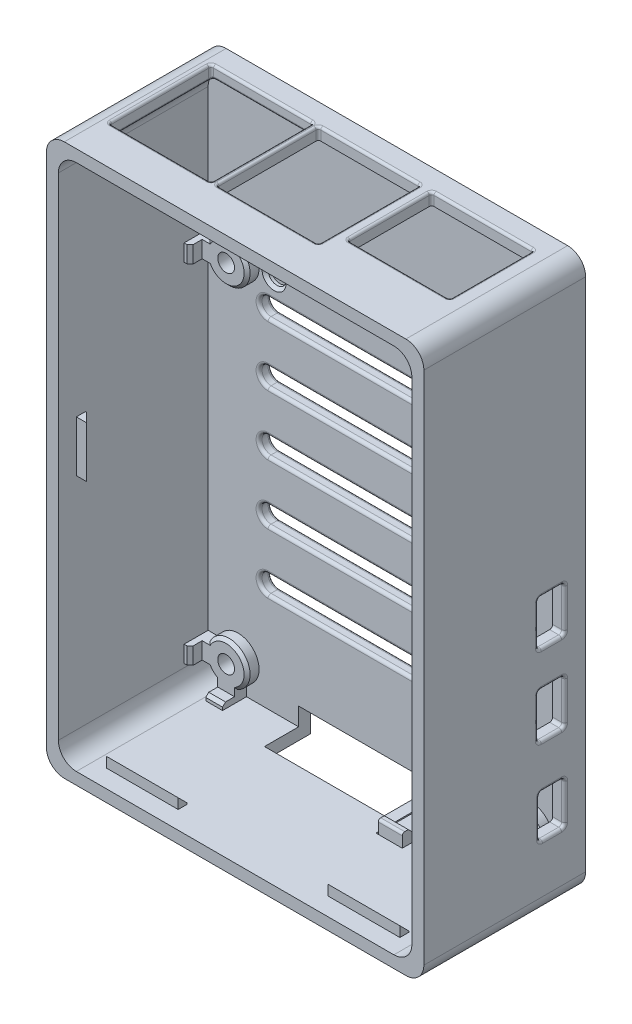
SolidWorks part; units mm, degrees
ref_plane "Front Plane" through (0, 0, 0) normal (1, 0, 0) x (0, 1, 0)
ref_plane "Top Plane" through (0, 0, 0) normal (0, 0, 1) x (0, 1, 0)
ref_plane "Right Plane" through (0, 0, 0) normal (0, 1, 0) x (-1, 0, 0)
sketch "Sketch2" plane through (0, 0, 0) normal (0, 0, 1) x (0, 1, 0)
  line L0 (14.7849, 61.5661) -> (117.7419, 61.5661) construction
  line L1 (-0.0095, 29.4958) -> (120.0951, 29.4958) construction
  line L2 (2.9905, 58.9958) -> (84.9905, 58.9958)
  line L3 (-0.0095, 55.9958) -> (-0.0095, 2.9958)
  line L4 (2.9905, -0.0042) -> (84.9905, -0.0042)
  line L5 (87.9905, 55.9958) -> (87.9905, 2.9958)
  line L6 (33.9905, 95.81) -> (33.9905, -24.3082) construction
  line L7 (43.9905, 95.8142) -> (43.9905, -24.3041) construction
  line L8 (62.9905, 69.2818) -> (62.9905, -9.286) construction
  line L9 (67.9905, 48.9958) -> (67.9905, 9.9958) construction
  line L10 (69.4905, 48.9958) -> (69.4905, 9.9958)
  line L11 (66.4905, 48.9958) -> (66.4905, 9.9958)
  line L12 (57.9905, 48.9958) -> (57.9905, 9.9958) construction
  line L13 (56.4905, 48.9958) -> (56.4905, 9.9958)
  line L14 (59.4905, 48.9958) -> (59.4905, 9.9958)
  line L18 (52.9905, 69.2818) -> (52.9905, -9.286) construction
  line L19 (47.9905, 48.9958) -> (47.9905, 9.9958) construction
  line L20 (49.4905, 48.9958) -> (49.4905, 9.9958)
  line L21 (46.4905, 48.9958) -> (46.4905, 9.9958)
  line L22 (42.9905, 69.2818) -> (42.9905, -9.286) construction
  line L23 (37.9905, 48.9958) -> (37.9905, 9.9958) construction
  line L24 (36.4905, 48.9958) -> (36.4905, 9.9958)
  line L25 (39.4905, 48.9958) -> (39.4905, 9.9958)
  line L26 (32.9905, 69.2818) -> (32.9905, -9.286) construction
  line L27 (27.9905, 48.9958) -> (27.9905, 9.9958) construction
  line L28 (29.4905, 48.9958) -> (29.4905, 9.9958)
  line L29 (26.4905, 48.9958) -> (26.4905, 9.9958)
  line L30 (22.9905, 69.2818) -> (22.9905, -9.286) construction
  line L31 (17.9905, 48.9958) -> (17.9905, 9.9958) construction
  line L32 (16.4905, 48.9958) -> (16.4905, 9.9958)
  line L33 (19.4905, 48.9958) -> (19.4905, 9.9958)
  line L34 (3.5905, 58.9958) -> (3.5905, 57.2036)
  line L35 (0.9905, 60.9958) -> (86.9905, 60.9958)
  line L36 (-2.0095, 57.9958) -> (-2.0095, 0.9958)
  line L37 (0.9905, -2.0042) -> (86.9905, -2.0042)
  line L38 (89.9905, 57.9958) -> (89.9905, 0.9958)
  line L39 (6.3905, 58.9958) -> (6.3905, 57.2036)
  line L40 (3.5905, 57.9958) -> (6.3905, 57.9958)
  line L41 (3.5905, 0.9958) -> (6.3905, 0.9958)
  line L42 (6.3905, -0.0042) -> (6.3905, 1.788)
  line L43 (3.5905, -0.0042) -> (3.5905, 1.788)
  line L44 (64.3905, 0.9958) -> (61.5905, 0.9958)
  line L45 (64.3905, -0.0042) -> (64.3905, 1.788)
  line L46 (61.5905, -0.0042) -> (61.5905, 1.788)
  line L47 (64.3905, 58.9958) -> (64.3905, 57.2036)
  line L48 (64.3905, 57.9958) -> (61.5905, 57.9958)
  line L49 (61.5905, 58.9958) -> (61.5905, 57.2036)
  line L50 (-0.0095, 55.3958) -> (1.7827, 55.3958)
  line L51 (10.4268, 53.9958) -> (-6.5581, 53.9958) construction
  line L52 (-0.0095, 52.5958) -> (1.7827, 52.5958)
  line L53 (0.9905, 55.3958) -> (0.9905, 52.5958)
  line L54 (0.9905, 3.5958) -> (0.9905, 6.3958)
  line L55 (-0.0095, 3.5958) -> (1.7827, 3.5958)
  line L56 (-0.0095, 6.3958) -> (1.7827, 6.3958)
  circle A0 centre (4.9905, 53.9958) radius 1.4
  circle A1 centre (4.9905, 4.9958) radius 1.4
  circle A2 centre (62.9905, 4.9958) radius 1.4
  circle A3 centre (62.9905, 53.9958) radius 1.4
  arc A4 (3.5905, 57.2036) -> (1.7827, 55.3958) centre (4.9905, 53.9958) ccw
  arc A7 (3.5905, 1.788) -> (1.7827, 3.5958) centre (4.9905, 4.9958) cw
  arc A8 (64.3905, 1.788) -> (61.5905, 1.788) centre (62.9905, 4.9958) ccw
  arc A9 (64.3905, 57.2036) -> (61.5905, 57.2036) centre (62.9905, 53.9958) cw
  arc A10 (2.9905, 58.9958) -> (-0.0095, 55.9958) centre (2.9905, 55.9958) ccw
  arc A11 (2.9905, -0.0042) -> (-0.0095, 2.9958) centre (2.9905, 2.9958) cw
  arc A12 (84.9905, -0.0042) -> (87.9905, 2.9958) centre (84.9905, 2.9958) ccw
  arc A13 (84.9905, 58.9958) -> (87.9905, 55.9958) centre (84.9905, 55.9958) cw
  circle A14 centre (4.9905, 10.9958) radius 1.5
  circle A15 centre (62.9905, 47.9958) radius 1.5
  arc A16 (69.4905, 48.9958) -> (66.4905, 48.9958) centre (67.9905, 48.9958) ccw
  arc A17 (66.4905, 9.9958) -> (69.4905, 9.9958) centre (67.9905, 9.9958) ccw
  arc A18 (56.4905, 48.9958) -> (59.4905, 48.9958) centre (57.9905, 48.9958) cw
  arc A19 (59.4905, 9.9958) -> (56.4905, 9.9958) centre (57.9905, 9.9958) cw
  arc A22 (49.4905, 48.9958) -> (46.4905, 48.9958) centre (47.9905, 48.9958) ccw
  arc A23 (46.4905, 9.9958) -> (49.4905, 9.9958) centre (47.9905, 9.9958) ccw
  arc A24 (36.4905, 48.9958) -> (39.4905, 48.9958) centre (37.9905, 48.9958) cw
  arc A25 (39.4905, 9.9958) -> (36.4905, 9.9958) centre (37.9905, 9.9958) cw
  arc A26 (29.4905, 48.9958) -> (26.4905, 48.9958) centre (27.9905, 48.9958) ccw
  arc A27 (26.4905, 9.9958) -> (29.4905, 9.9958) centre (27.9905, 9.9958) ccw
  arc A28 (16.4905, 48.9958) -> (19.4905, 48.9958) centre (17.9905, 48.9958) cw
  arc A29 (19.4905, 9.9958) -> (16.4905, 9.9958) centre (17.9905, 9.9958) cw
  arc A30 (0.9905, 60.9958) -> (-2.0095, 57.9958) centre (0.9905, 57.9958) ccw
  arc A31 (86.9905, 60.9958) -> (89.9905, 57.9958) centre (86.9905, 57.9958) cw
  arc A32 (86.9905, -2.0042) -> (89.9905, 0.9958) centre (86.9905, 0.9958) ccw
  arc A33 (0.9905, -2.0042) -> (-2.0095, 0.9958) centre (0.9905, 0.9958) cw
  arc A34 (1.7827, 52.5958) -> (6.3905, 57.2036) centre (4.9905, 53.9958) ccw
  arc A35 (1.7827, 6.3958) -> (6.3905, 1.788) centre (4.9905, 4.9958) cw
  point P40 (67.9905, 29.4958)
  point P47 (57.9905, 29.4958)
  point P63 (47.9905, 29.4958)
  point P72 (37.9905, 29.4958)
  point P81 (27.9905, 29.4958)
  point P90 (17.9905, 29.4958)
  point P111 (3.5905, 58.0997)
  dimension "D3" = 2.8
  dimension "D7" = 7
  dimension "D8" = 6
  dimension "D9" = 3
  dimension "D12" = 3
  dimension "D26" = 6.4
  dimension "D2" = 10
  dimension "D4" = 5
  dimension "D5" = 5
  dimension "D6" = 29
  dimension "D10" = 6
  dimension "D11" = 5
  dimension "D13" = 6
  dimension "D14" = 10
  dimension "D15" = 2.8
  dimension "D16" = 10
  dimension "D17" = 3
  dimension "D18" = 10
  dimension "D19" = 10
  dimension "D20" = 10
  dimension "D21" = 10
  dimension "D22" = 2
  dimension "D23" = 2
  dimension "D24" = 92
  dimension "D25" = 63
  dimension "D27" = 1
  dimension "D28" = 1.4
  dimension "D29" = 1
extrude "Boss-Extrude1" add sketch "Sketch2" along normal blind 25 contours L36 A33 L37 A32 L38 A31 L35 A30 | L3 A11 L4 A12 L5 A13 L2 A10
extrude "Boss-Extrude2" add sketch "Sketch2<6>" against normal blind 2 contours L36 A33 L37 A32 L38 A31 L35 A30
sketch "Sketch2<6>" plane through (0, 0, 0) normal (0, 0, 1) x (0, 1, 0) same geometry as "Sketch2"
extrude "Cut-Extrude1" cut sketch "Sketch2<7>" against normal blind 2 contours L11 A17 L10 A16 | L13 A19 L14 A18 | L21 A23 L20 A22 | L24 A25 L25 A24 | L29 A27 L28 A26 | L32 A29 L33 A28
sketch "Sketch2<7>" plane through (0, 0, 0) normal (0, 0, 1) x (0, 1, 0) same geometry as "Sketch2"
extrude "Boss-Extrude10" add sketch "Sketch2<24>" along normal blind 2 contours L52 A34 L39 L40 L34 A4 L50 L53 A0 | A9 L47 L48 L49 A3 | L45 A8 L46 L44 A2 | A35 L56 L54 L55 A7 L43 L41 L42 A1 region at (-57.8898, 4.9905, 0) region at (-57.8932, 62.9905, 0) region at (-6.2898, 1.3866, 0) region at (-1.0984, 62.9905, 0)
sketch "Sketch2<24>" plane through (0, 0, 0) normal (0, 0, 1) x (0, 1, 0) same geometry as "Sketch2"
extrude "Boss-Extrude13" add sketch "Sketch2<29>" along normal blind 4 contours L34 L40 L39 L2 | L53 L50 L3 L52 | L56 L3 L55 L54 | L43 L4 L42 L41 | L46 L4 L45 L44 | L2 L49 L48 L47 region at (-58.4958, 4.9905, 0) region at (-53.9958, 0.4905, 0) region at (-58.4958, 62.9905, 0) region at (-4.9958, 0.4905, 0) region at (-0.4958, 4.9905, 0) region at (-0.4958, 62.9905, 0)
sketch "Sketch2<29>" plane through (0, 0, 0) normal (0, 0, 1) x (0, 1, 0) same geometry as "Sketch2"
chamfer "Chamfer4" distance 0.5 angle 45 6 edges at (-57.9958, 62.9905, 4) (-0.9958, 62.9905, 4) (-4.9958, 0.9905, 4) (-0.9958, 4.9905, 4) (-53.9958, 0.9905, 4) (-57.9958, 4.9905, 4)
chamfer "Chamfer5" distance 0.5 angle 45 6 edges at (-8.4958, 62.9905, 2) (-7.4707, 7.4653, 2) (-2.5209, 2.5156, 2) (-56.4707, 2.5156, 2) (-51.5209, 7.4653, 2) (-50.4958, 62.9905, 2)
fillet "Fillet2" radius 0.5 48 edges at (-50.4958, 67.9905, 0) (-29.4958, 69.4905, 0) (-8.4958, 67.9905, 0) (-50.4958, 67.9905, -2) (-29.4958, 69.4905, -2) (-8.4958, 67.9905, -2) (-50.4958, 57.9905, 0) (-29.4958, 59.4905, 0) (-8.4958, 57.9905, 0) (-50.4958, 57.9905, -2) (-29.4958, 59.4905, -2) (-8.4958, 57.9905, -2) (-50.4958, 47.9905, 0) (-29.4958, 49.4905, 0) (-8.4958, 47.9905, 0) (-50.4958, 47.9905, -2) (-29.4958, 49.4905, -2) (-8.4958, 47.9905, -2) (-50.4958, 17.9905, -2) (-29.4958, 19.4905, -2) (-8.4958, 17.9905, -2) (-50.4958, 27.9905, -2) (-29.4958, 29.4905, -2) (-8.4958, 27.9905, -2) (-50.4958, 37.9905, -2) (-29.4958, 39.4905, -2) (-8.4958, 37.9905, -2) (-50.4958, 37.9905, 0) (-29.4958, 39.4905, 0) (-8.4958, 37.9905, 0) (-50.4958, 27.9905, 0) (-29.4958, 29.4905, 0) (-8.4958, 27.9905, 0) (-50.4958, 17.9905, 0) (-29.4958, 19.4905, 0) (-8.4958, 17.9905, 0) (-29.4958, 66.4905, 0) (-29.4958, 66.4905, -2) (-29.4958, 56.4905, 0) (-29.4958, 56.4905, -2) (-29.4958, 46.4905, 0) (-29.4958, 46.4905, -2) (-29.4958, 16.4905, -2) (-29.4958, 26.4905, -2) (-29.4958, 36.4905, -2) (-29.4958, 36.4905, 0) (-29.4958, 26.4905, 0) (-29.4958, 16.4905, 0)
extrude "Cut-Extrude10" cut sketch "Sketch2<34>" against normal blind 1 contours A14 | A15
sketch "Sketch2<34>" plane through (0, 0, 0) normal (0, 0, 1) x (0, 1, 0) same geometry as "Sketch2"
chamfer "Chamfer6" distance 0.5 angle 45 2 edges at (-9.4958, 4.9905, 0) (-46.4958, 62.9905, 0)
sketch "Sketch5" plane through (0, -0.0095, 0) normal (0, 1, 0) x (-1, 0, 0)
  line L0 (17.8958, 5.7) -> (21.8958, 5.7)
  line L1 (0.9958, 25) -> (0.9958, -2) construction
  line L2 (57.9958, -2) -> (0.9958, -2) construction
  line L3 (17.8958, 5.7) -> (17.8958, 8.7)
  line L4 (17.8958, 8.7) -> (21.8958, 8.7)
  line L5 (21.8958, 8.7) -> (21.8958, 5.7)
  line L6 (17.8958, 5.7) -> (17.8958, -2)
  line L7 (21.8958, 5.7) -> (21.8958, -2)
  line L8 (17.8958, -2) -> (21.8958, -2)
  line L9 (17.6958, -2) -> (17.6958, 8.9)
  line L10 (17.6958, 8.9) -> (22.0958, 8.9)
  line L11 (22.0958, 8.9) -> (22.0958, -2)
  line L12 (17.6958, -2) -> (17.8958, -2)
  line L13 (21.8958, -2) -> (22.0958, -2)
  line L14 (23.8958, 5.7) -> (43.8958, 5.7)
  line L15 (23.8958, 5.7) -> (23.8958, -2)
  line L16 (23.8958, -2) -> (43.8958, -2)
  line L17 (43.8958, -2) -> (43.8958, 5.7)
  line L18 (57.9958, 25) -> (57.9958, -2) construction
  line L19 (4.9958, 22) -> (16.9958, 22)
  line L20 (4.9958, 22) -> (4.9958, 20.5)
  line L21 (4.9958, 20.5) -> (16.9958, 20.5)
  line L22 (16.9958, 22) -> (16.9958, 20.5)
  line L23 (41.9958, 22) -> (53.9958, 22)
  line L24 (41.9958, 22) -> (41.9958, 20.5)
  line L25 (41.9958, 20.5) -> (53.9958, 20.5)
  line L26 (53.9958, 22) -> (53.9958, 20.5)
  line L27 (57.9958, 25) -> (0.9958, 25) construction
  line M4 (6.3958, 0) -> (52.5958, 0)
  dimension "D1" = 7.7
  dimension "D2" = 16.9
  dimension "D3" = 4
  dimension "D4" = 3
  dimension "D5" = 0.2
  dimension "D6" = 0.2
  dimension "D7" = 0.2
  dimension "D8" = 20
  dimension "D9" = 2
  dimension "D10" = 4
  dimension "D11" = 12
  dimension "D12" = 4
  dimension "D13" = 12
  dimension "D14" = 1.5
  dimension "D15" = 1.5
  dimension "D16" = 3
  dimension "D17" = 3
extrude "Boss-Extrude15" add sketch "Sketch5" along normal blind 2 contours L5 L4 L3 L0 region at (-19.8958, -0.0095, 7.2)
fillet "Fillet4" radius 0.4 1 edges at (-19.8958, 1.9905, 8.7)
chamfer "Chamfer8" distance 2 angle 45 1 edges at (-19.8958, 1.9905, 5.7)
extrude "Cut-Extrude12" cut sketch "Sketch5<6>" against normal blind 4 and the other way blind 1.5 contours L7 L13 L11 M4 | L9 L12 L6 M4 | L11 L10 L9 L6 L3 L4 L5 L7 M4 region at (-17.7965, -0.0095, 2.85) region at (-17.7958, -0.0095, -1) region at (-21.9958, -0.0095, -1)
sketch "Sketch5<6>" plane through (0, -0.0095, 0) normal (0, 1, 0) x (-1, 0, 0) same geometry as "Sketch5"
extrude "Cut-Extrude15" cut sketch "Sketch5<10>" against normal blind 4 and the other way blind 3 contours L17 L14 L15 M4 | L16 L17 L15 M4 region at (-33.8958, -0.0095, 2.85) region at (-33.8958, -0.0095, -1)
sketch "Sketch5<10>" plane through (0, -0.0095, 0) normal (0, 1, 0) x (-1, 0, 0) same geometry as "Sketch5"
sketch "Sketch6" plane through (0, 89.9905, 0) normal (0, 1, 0) x (-1, 0, 0)
  line L0 (3.1958, 15.5) -> (20.1958, 15.5)
  line L1 (0.9958, 25) -> (0.9958, -2) construction
  line L2 (57.9958, -2) -> (0.9958, -2) construction
  line L3 (3.1958, 15.5) -> (3.1958, 1.5)
  line L4 (3.1958, 1.5) -> (20.1958, 1.5)
  line L5 (20.1958, 1.5) -> (20.1958, 15.5)
  line L6 (57.9958, 25) -> (0.9958, 25) construction
  line L7 (22.0958, 18.5) -> (39.0958, 18.5)
  line L8 (22.0958, 18.5) -> (22.0958, 1.5)
  line L9 (22.0958, 1.5) -> (39.0958, 1.5)
  line L10 (39.0958, 18.5) -> (39.0958, 1.5)
  line L11 (39.9958, 18.5) -> (56.9958, 18.5)
  line L12 (39.9958, 18.5) -> (39.9958, 1.5)
  line L13 (39.9958, 1.5) -> (56.9958, 1.5)
  line L14 (56.9958, 18.5) -> (56.9958, 1.5)
  line L15 (4.9958, 22) -> (16.9958, 22)
  line L16 (4.9958, 22) -> (4.9958, 20.5)
  line L17 (4.9958, 20.5) -> (16.9958, 20.5)
  line L18 (16.9958, 22) -> (16.9958, 20.5)
  line L19 (41.9958, 22) -> (53.9958, 22)
  line L20 (41.9958, 22) -> (41.9958, 20.5)
  line L21 (41.9958, 20.5) -> (53.9958, 20.5)
  line L22 (53.9958, 22) -> (53.9958, 20.5)
  line L24 (57.9958, 25) -> (57.9958, -2) construction
  dimension "D1" = 17
  dimension "D2" = 2.2
  dimension "D3" = 3.5
  dimension "D4" = 14
  dimension "D5" = 17
  dimension "D6" = 17
  dimension "D7" = 21.1
  dimension "D8" = 3.5
  dimension "D9" = 17
  dimension "D10" = 39
  dimension "D11" = 3.5
  dimension "D12" = 17
  dimension "D13" = 3
  dimension "D14" = 3
  dimension "D15" = 12
  dimension "D16" = 12
  dimension "D17" = 1.5
  dimension "D18" = 1.5
  dimension "D19" = 4
  dimension "D20" = 4
extrude "Cut-Extrude16" cut sketch "Sketch6" against normal blind 4 and the other way blind 4 contours L4 L5 L0 L3 | L10 L7 L8 L9 | L14 L11 L12 L13 | L5 L0 L3 L4 | L8 L7 L10 L9 | L12 L11 L14 L13 region at (-11.6958, 89.9905, 8.5) region at (-30.5958, 89.9905, 10) region at (-48.4958, 89.9905, 10)
fillet "Fillet6" radius 0.4 30 edges at (-56.9958, 87.8189, 10) (-56.5031, 87.9473, 18.5) (-56.5031, 87.9473, 1.5) (-47.9958, 87.9905, 18.5) (-39.9958, 89.9905, 10) (-47.9958, 87.9905, 1.5) (-56.9958, 89.9905, 10) (-11.6958, 89.9905, 1.5) (-56.9958, 88.9047, 18.5) (-39.9958, 88.9905, 18.5) (-39.9958, 88.9905, 1.5) (-39.9958, 87.9905, 10) (-48.4958, 89.9905, 18.5) (-48.4958, 89.9905, 1.5) (-56.9958, 88.9047, 1.5) (-39.0958, 88.9905, 1.5) (-39.0958, 88.9905, 18.5) (-22.0958, 88.9905, 18.5) (-22.0958, 88.9905, 1.5) (-39.0958, 89.9905, 10) (-30.5958, 89.9905, 1.5) (-22.0958, 89.9905, 10) (-30.5958, 89.9905, 18.5) (-3.1958, 88.9905, 15.5) (-20.1958, 88.9905, 15.5) (-20.1958, 88.9905, 1.5) (-20.1958, 89.9905, 8.5) (-3.1958, 88.9905, 1.5) (-11.6958, 89.9905, 15.5) (-3.1958, 89.9905, 8.5)
sketch "Sketch7" plane through (2.0042, 0, 0) normal (1, 0, 0) x (0, 1, 0)
  line L0 (9.1905, 5.7) -> (13.8943, 5.7)
  line L1 (13.8943, 5.7) -> (16.1905, 5.7)
  line L2 (16.1905, 5.7) -> (16.1905, 1.5)
  line L3 (16.1905, 1.5) -> (9.1905, 1.5)
  line L4 (9.1905, 1.5) -> (9.1905, 5.7)
  line L5 (0.9905, 25) -> (0.9905, -2) construction
  line L6 (0.9905, -2) -> (86.9905, -2) construction
  line L8 (23.5905, 5.9) -> (30.9905, 5.9)
  line L9 (23.5905, 5.9) -> (23.5905, 1.5)
  line L10 (23.5905, 1.5) -> (30.9905, 1.5)
  line L11 (30.9905, 5.9) -> (30.9905, 1.5)
  line L12 (36.9905, 5.9) -> (44.3905, 5.9)
  line L13 (36.9905, 5.9) -> (36.9905, 1.5)
  line L14 (36.9905, 1.5) -> (44.3905, 1.5)
  line L15 (44.3905, 5.9) -> (44.3905, 1.5)
  line L16 (39.7405, 22) -> (48.2405, 22)
  line L17 (39.7405, 22) -> (39.7405, 20.5)
  line L18 (39.7405, 20.5) -> (48.2405, 20.5)
  line L19 (48.2405, 22) -> (48.2405, 20.5)
  line L21 (0.9905, 25) -> (86.9905, 25) construction
  dimension "D1" = 8.2
  dimension "D2" = 7
  dimension "D3" = 3.5
  dimension "D4" = 4.2
  dimension "D5" = 22.6
  dimension "D6" = 7.4
  dimension "D7" = 4.4
  dimension "D8" = 3.5
  dimension "D9" = 36
  dimension "D10" = 3.5
  dimension "D11" = 4.4
  dimension "D12" = 7.4
  dimension "D13" = 8.5
  dimension "D14" = 38.75
  dimension "D15" = 1.5
  dimension "D16" = 3
extrude "Cut-Extrude18" cut sketch "Sketch7" against normal blind 4 and the other way blind 4 contours L4 L3 L2 L1 L0 | L11 L8 L9 L10 | L15 L12 L13 L14 region at (2.0042, 12.6905, 3.6) region at (2.0042, 27.2905, 3.7) region at (2.0042, 40.6905, 3.7)
fillet "Fillet7" radius 0.5 24 edges at (2.0042, 44.3905, 3.7) (2.0042, 36.9905, 3.7) (2.0042, 23.5905, 3.7) (2.0042, 30.9905, 3.7) (2.0042, 16.1905, 3.6) (2.0042, 9.1905, 3.6) (1.0042, 16.1905, 5.7) (1.0042, 30.9905, 5.9) (1.0042, 44.3905, 5.9) (1.0042, 9.1905, 1.5) (1.0042, 23.5905, 1.5) (1.0042, 36.9905, 1.5) (2.0042, 40.6905, 1.5) (2.0042, 40.6905, 5.9) (2.0042, 27.2905, 5.9) (2.0042, 27.2905, 1.5) (2.0042, 12.6905, 1.5) (2.0042, 12.6905, 5.7) (1.0042, 44.3905, 1.5) (1.0042, 30.9905, 1.5) (1.0042, 16.1905, 1.5) (1.0042, 9.1905, 5.7) (1.0042, 23.5905, 5.9) (1.0042, 36.9905, 5.9)
sketch "Sketch10" plane through (-60.9958, 0, 0) normal (-1, 0, 0) x (0, -1, 0)
  line L0 (-86.9905, 25) -> (-86.9905, -2) construction
  line L1 (-48.2405, 22) -> (-39.7405, 22)
  line L2 (-48.2405, 22) -> (-48.2405, 20.5)
  line L3 (-48.2405, 20.5) -> (-39.7405, 20.5)
  line L4 (-39.7405, 22) -> (-39.7405, 20.5)
  line L5 (-0.9905, 25) -> (-86.9905, 25) construction
  dimension "D1" = 38.75
  dimension "D2" = 8.5
  dimension "D3" = 1.5
  dimension "D4" = 3
extrude "Boss-Extrude18" add sketch "Sketch10" against normal blind 4
extrude "Boss-Extrude19" add sketch "Sketch7<6>" against normal blind 4 contours L19 L16 L17 L18 region at (2.0042, 43.9905, 21.25)
sketch "Sketch7<6>" plane through (2.0042, 0, 0) normal (1, 0, 0) x (0, 1, 0) same geometry as "Sketch7"
extrude "Boss-Extrude20" add sketch "Sketch6<3>" against normal blind 4 contours L22 L19 L20 L21 | L17 L18 L15 L16 region at (-47.9958, 89.9905, 21.25)
sketch "Sketch6<3>" plane through (0, 89.9905, 0) normal (0, 1, 0) x (-1, 0, 0) same geometry as "Sketch6"
extrude "Boss-Extrude21" add sketch "Sketch5<11>" along normal blind 2 contours L22 L19 L20 L21 | L26 L23 L24 L25 region at (-10.9958, -0.0095, 21.25) region at (-47.9958, -0.0095, 21.25)
sketch "Sketch5<11>" plane through (0, -0.0095, 0) normal (0, 1, 0) x (-1, 0, 0) same geometry as "Sketch5"
chamfer "Chamfer9" distance 1.8 angle 45 6 edges at (-56.9958, 43.9905, 20.5) (-47.9958, 85.9905, 20.5) (-10.9958, 85.9905, 20.5) (-10.9958, 1.9905, 20.5) (-47.9958, 1.9905, 20.5) (-1.9958, 43.9905, 20.5)
